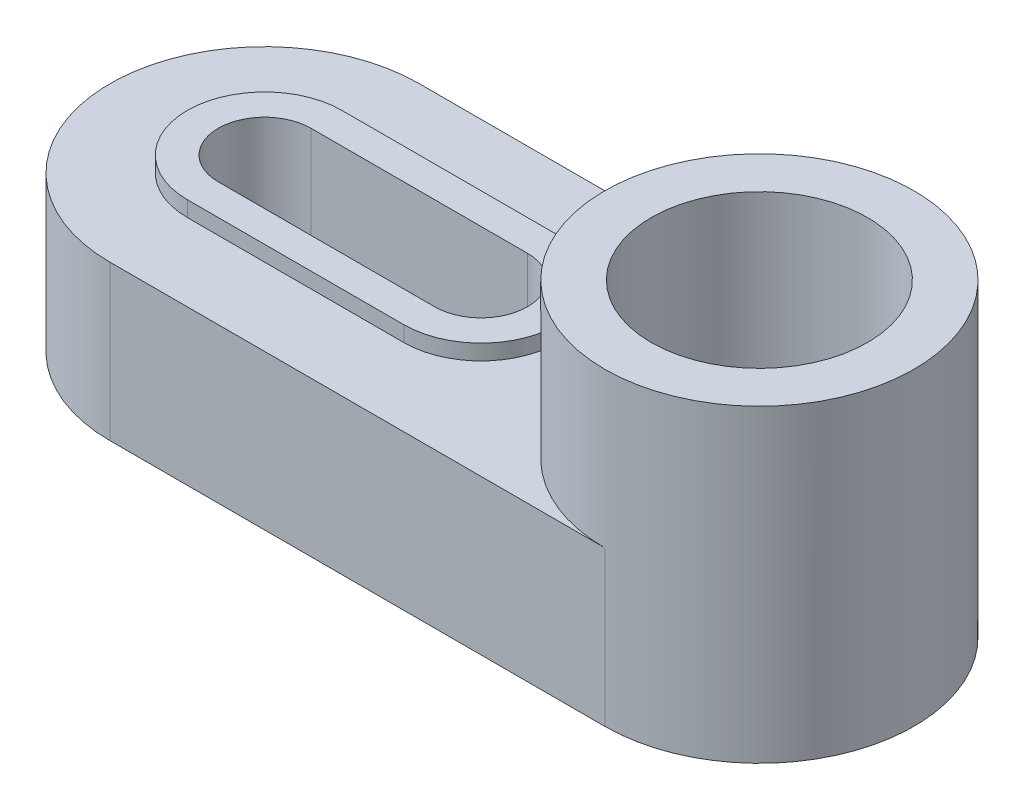
SolidWorks part; units mm, degrees
ref_plane "前视基准面" through (0, 0, 0) normal (0, 0, 1) x (1, 0, 0)
ref_plane "上视基准面" through (0, 0, 0) normal (0, 1, 0) x (1, 0, 0)
ref_plane "右视基准面" through (0, 0, 0) normal (1, 0, 0) x (0, 0, -1)
other "Configuration Table"
sketch "草图1" plane through (0, 0, 0) normal (0, 1, 0) x (1, 0, 0)
  line L0 (-6.9038, 0) -> (25.0962, 0) construction
  line L1 (-6.9038, 10) -> (25.0962, 10)
  line L2 (-6.9038, -10) -> (25.0962, -10)
  line L3 (-6.9038, 0) -> (-6.9038, 10) construction
  line L4 (25.0962, 0) -> (25.0962, 10) construction
  line L5 (-6.9038, 0) -> (7.0962, 0) construction
  line L6 (-6.9038, 5) -> (7.0962, 5)
  line L7 (-6.9038, -5) -> (7.0962, -5)
  line L8 (-6.9038, 0) -> (7.0962, 0) construction
  line L9 (-6.9038, 3) -> (7.0962, 3)
  line L10 (-6.9038, -3) -> (7.0962, -3)
  arc A0 (-6.9038, 10) -> (-6.9038, -10) centre (-6.9038, 0) ccw
  arc A1 (25.0962, -10) -> (25.0962, 10) centre (25.0962, 0) ccw
  arc A2 (-6.9038, 5) -> (-6.9038, -5) centre (-6.9038, 0) ccw
  arc A3 (7.0962, -5) -> (7.0962, 5) centre (7.0962, 0) ccw
  arc A4 (-6.9038, 3) -> (-6.9038, -3) centre (-6.9038, 0) ccw
  arc A5 (7.0962, -3) -> (7.0962, 3) centre (7.0962, 0) ccw
  circle A6 centre (25.0962, 0) radius 10
  circle A7 centre (25.0962, 0) radius 7
  point P3 (9.0962, 0)
  point P12 (0.0962, 0)
  point P20 (0.0962, 0)
  dimension "D1" = 10
  dimension "D4" = 5
  dimension "D5" = 3
  dimension "D6" = 14
  dimension "D2" = 32
  dimension "D3" = 14
extrude "凸台-拉伸1" add sketch "草图1" along normal blind 10 contours A6 L1 A0 L2 A3 L7 A2 L6 region at (9.0962, 0, -9.5348)
extrude "凸台-拉伸2" add sketch "草图1<5>" along normal blind 20 contours A1 A6 A7 region at (31.9673, 0, -6.8711)
sketch "草图1<5>" plane through (0, 0, 0) normal (0, 1, 0) x (1, 0, 0) same geometry as "草图1"
extrude "凸台-拉伸3" add sketch "草图1<6>" along normal blind 11 contours L9 A5 L10 A4 | A3 L6 A2 L7
sketch "草图1<6>" plane through (0, 0, 0) normal (0, 1, 0) x (1, 0, 0) same geometry as "草图1"
